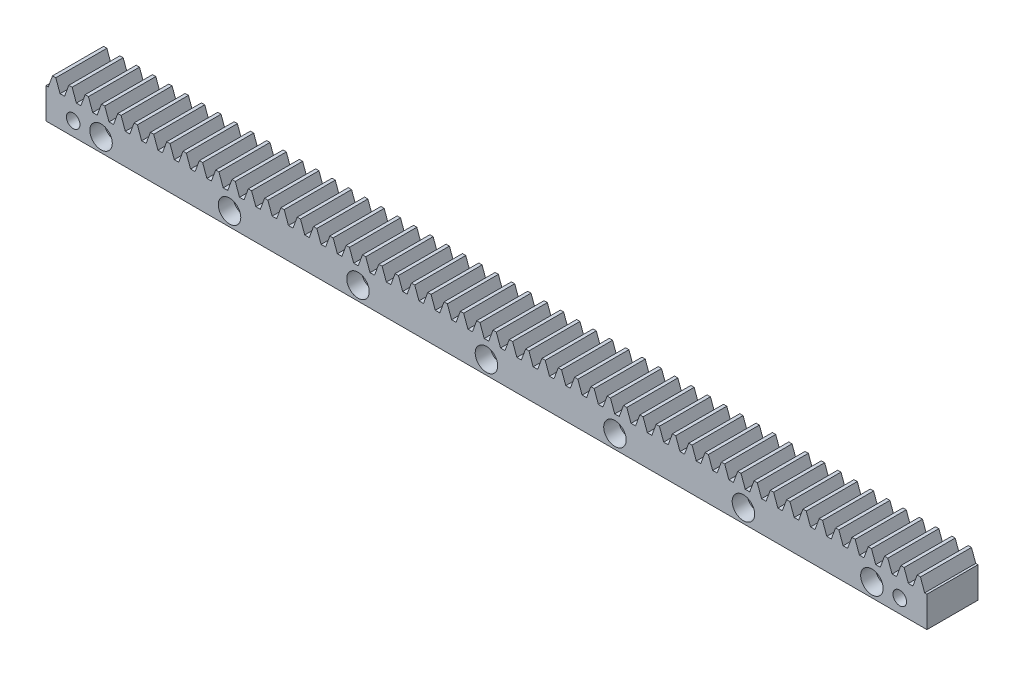
SolidWorks part; units mm, degrees
extrude "Blank" add sketch "BlankSke" against normal blind 59
sketch "BlankSke" plane through (0, 0, 0) normal (0, 0, 1) x (1, 0, 0)
  line L1 (0, 0) -> (1017.88, 0)
  line L2 (0, 0) -> (0, 49)
  line L3 (0, 49) -> (1017.88, 49)
  line L4 (1017.88, 0) -> (1017.88, 49)
  dimension "Length" = 1017.88
ref_plane "Plane1" through (0, 0, 0) normal (0, 0, 1) x (1, 0, 0)
ref_plane "Plane2" through (0, 0, 0) normal (0, 1, 0) x (1, 0, 0)
ref_plane "Plane3" through (0, 0, 0) normal (1, 0, 0) x (0, 0, -1)
sketch "HoldingSke" plane through (0, 0, 0) normal (0, 1, 0) x (1, 0, 0)
  line L0 (0, 0) -> (0.0232, 0.165)
  line L1 (-15, 0) -> (100, 0) construction
  line L2 (0, 0) -> (-2.1039, 2.3779)
  line L3 (0, 0) -> (-11.863, 4.5341)
  line L4 (0, 0) -> (4.8292, 7.1596)
  line L5 (0, 0) -> (-23.7986, -8.8762)
  line L6 (0, 0) -> (-10.5278, -7.1032)
  line L9 (-71.009, 38.7566) -> (885.4854, 386.8921)
  line L10 (-76.2, 8.3779) -> (-33.2, 8.3779)
  line L11 (0, 0) -> (-59, 0)
  line L12 (-76.2, 101.6) -> (-75.993, 101.6)
  line L13 (24.9733, 27.94) -> (52.9518, 28.4284)
  line L14 (24.9733, 27.94) -> (24.9743, 27.94)
  line L15 (24.9733, 27.94) -> (100.4006, 29.5858)
  circle A0 centre (0, 0) radius 19.05
  circle A1 centre (0, 0) radius 21.5
  circle A2 centre (0, 0) radius 12.7
  dimension "Num_teeth" = 56
  dimension "Width" = 59
  dimension "Length" = 1017.88
  dimension "Pitch_height" = 43
sketch "TooCutSkeIll" plane through (0, 0, 0) normal (0, 0, 1) x (1, 0, 0)
  line L0 (-7.4597, 48.8421) -> (-2.9631, 36.4876)
  line L1 (-1.5526, 35.5) -> (1.5526, 35.5)
  line L2 (2.9631, 36.4876) -> (7.4597, 48.8421)
  line L3 (1017.88, 49) -> (0, 49) construction
  line L4 (0, 0) -> (0, 64.897) construction
  line L5 (-13.208, 43) -> (12.954, 43) construction
  line L6 (0, 0) -> (1017.88, 0) construction
  line L7 (5.3334, 43) -> (5.3334, 48.7463) construction
  line L8 (-5.3334, 43) -> (-5.3334, 48.7463) construction
  line L9 (7.6853, 49) -> (7.6853, 49.0254)
  line L10 (-7.6853, 49) -> (-7.6853, 49.0254)
  line L11 (-7.6853, 49.0254) -> (7.6853, 49.0254)
  arc A0 (1.5526, 35.5) -> (2.9631, 36.4876) centre (1.5526, 37.001) ccw
  arc A1 (-2.9631, 36.4876) -> (-1.5526, 35.5) centre (-1.5526, 37.001) ccw
  arc A2 (7.6853, 49) -> (7.4597, 48.8421) centre (7.6853, 48.76) ccw
  arc A3 (-7.4597, 48.8421) -> (-7.6853, 49) centre (-7.6853, 48.76) ccw
  dimension "Addendum_plus" = 6.0254
  dimension "Pitch_height" = 43
  dimension "Pressure_angle" = 20
  dimension "Gap_width" = 10.6668
  dimension "Dedendum" = 7.5
extrude "ToothCutIll" [suppressed] cut sketch "TooCutSkeIll" against normal through all
sketch "TooCutSkeSim" plane through (0, 0, 0) normal (0, 0, 1) x (1, 0, 0)
  line L0 (2.6036, 35.5) -> (-2.6036, 35.5)
  line L1 (7.5265, 49.0254) -> (2.6036, 35.5)
  line L2 (0, 17.4625) -> (0, 53.467) construction
  line L3 (7.5265, 49.0254) -> (-7.5265, 49.0254)
  line L6 (-7.5265, 49.0254) -> (-2.6036, 35.5)
  line L9 (-5.3334, 43) -> (5.3334, 43) construction
  line L10 (0, 0) -> (1017.88, 0) construction
  line L11 (5.3334, 43) -> (5.3334, 53.467) construction
  line L12 (-5.3334, 43) -> (-5.3334, 53.467) construction
  dimension "Addendum_plus" = 6.0254
  dimension "Pitch_height" = 43
  dimension "Pressure_angle" = 20
  dimension "Gap_width" = 10.6668
  dimension "Dedendum" = 7.5
extrude "ToothCutSim" cut sketch "TooCutSkeSim" against normal through all
pattern_linear "TeethCuts" count 56 spacing 18.8496 along (1, 0, 0) of "ToothCutIll", "ToothCutSim"
sketch "Sketch2" plane through (0, 0, 0) normal (0, 0, 1) x (1, 0, 0)
  line L0 (0, 35.5) -> (0, 0) construction
  line L1 (0, 0) -> (1017.88, 0) construction
  line L2 (1017.88, 0) -> (1017.88, 35.5) construction
  circle A0 centre (31.4, 16) radius 7.85
  circle A1 centre (986.48, 16) radius 7.85
  dimension "D1" = 15.7
  dimension "D5" = 15.7
  dimension "D2" = 31.4
  dimension "D3" = 16
  dimension "D4" = 16
  dimension "D6" = 31.4
extrude "Cut-Extrude1" cut sketch "Sketch2" against normal blind 202
sketch "Sketch3" plane through (0, 0, 0) normal (0, 0, 1) x (1, 0, 0)
  line L0 (0, 35.5) -> (0, 0) construction
  circle A0 centre (63.6, 16) radius 9
  dimension "D1" = 18
  dimension "D2" = 63.6
extrude "Cut-Extrude2" cut sketch "Sketch3" against normal blind 202
sketch "Sketch4" plane through (0, 0, 0) normal (0, 0, 1) x (1, 0, 0)
  circle A0 centre (63.6, 16) radius 13
  dimension "D1" = 26
extrude "Cut-Extrude3" cut sketch "Sketch4" against normal blind 17
sketch "Sketch5" plane through (0, 0, 0) normal (0, 0, 1) x (1, 0, 0)
  line L0 (63.6, 16) -> (31.4, 16)
  line L1 (986.48, 16) -> (954.28, 16)
  dimension "D1" = 32.2
  dimension "D2" = 32.2
pattern_linear "LPattern1" count 2 spacing 890.68 along (1, 0, 0) of "Cut-Extrude2", "Cut-Extrude3"
pattern_linear "LPattern2" count 6 spacing 148.4467 along (1, 0, 0) of "Cut-Extrude2", "Cut-Extrude3"
equation "' \"Module@HoldingSke\" = 6.35"
equation "' \"Num_teeth@HoldingSke\" = 12"
equation "' \"Ap@HoldingSke\" =  20"
equation "' \"Ap@HoldingSke\" = 20"
equation "' \"Width@HoldingSke\" = 0.25 * 25.4"
equation "' \"Show_teeth@HoldingSke\" = 500"
equation "' \"Backlash@HoldingSke\" = 0.009 * 25.4"
equation "' \"Addendum_fac@HoldingSke\" = 1.0"
equation "' \"Dedendum_fac@HoldingSke\" = 1.25"
equation "' \"Dedendum_add@HoldingSke\" = 0.00005 * 25.4"
equation "' \"Clearance_fac@HoldingSke\" = 0.25"
equation "' \"Pitch_height@HoldingSke\" = 1 * 25.4"
equation "' \"Length@HoldingSke\" = 4.71 * 25.4"
equation "\"Pitch@HoldingSke\" = 1 / \"Module@HoldingSke\""
equation "\"MPH@HoldingSke\" = \"Dedendum_fac@HoldingSke\" / \"Pitch@HoldingSke\" + 2 * \"Dedendum_add@HoldingSke\" + 0.002 * 25.4"
equation "\"MPH@HoldingSke\" = ((sgn( \"MPH@HoldingSke\" - \"Pitch_height@HoldingSke\")+1)*( \"MPH@HoldingSke\" - \"Pitch_height@HoldingSke\"))/2 + \"Pitch_height@HoldingSke\""
equation "\"Blank_height@BlankSke\" = \"Pitch_height@HoldingSke\" + \"Addendum_fac@HoldingSke\"  / \"Pitch@HoldingSke\" "
equation "\"Length@BlankSke\" =  \"Length@HoldingSke\""
equation "\"Face_width@Blank\" = \"Width@HoldingSke\""
equation "\"Pressure_angle@TooCutSkeIll\" = \"Ap@HoldingSke\""
equation "\"Addendum_plus@TooCutSkeIll\" =  \"Addendum_fac@HoldingSke\"  / \"Pitch@HoldingSke\" + 0.001 *25.4"
equation "\"Dedendum@TooCutSkeIll\" = \"Dedendum_fac@HoldingSke\"  / \"Pitch@HoldingSke\""
equation "\"Pitch_height@TooCutSkeIll\" =  \"MPH@HoldingSke\""
equation "\"Gap_width@TooCutSkeIll\" = 3.14159265 / 2 / \"Pitch@HoldingSke\" + 6 * \"Backlash@HoldingSke\""
equation "\"Pressure_angle@TooCutSkeSim\" = \"Ap@HoldingSke\""
equation "\"Addendum_plus@TooCutSkeSim\" =  \"Addendum_fac@HoldingSke\"  / \"Pitch@HoldingSke\" + 0.001 * 25.4"
equation "\"Dedendum@TooCutSkeSim\" = \"Dedendum_fac@HoldingSke\"  / \"Pitch@HoldingSke\""
equation "\"Pitch_height@TooCutSkeSim\" =  \"MPH@HoldingSke\""
equation "\"Gap_width@TooCutSkeSim\" = 3.14159265 / 2 / \"Pitch@HoldingSke\" + 6 * \"Backlash@HoldingSke\""
equation "\"Root_fillet@TooCutSkeIll\" = \"Clearance_fac@HoldingSke\" / \"Pitch@HoldingSke\" + \"Dedendum_add@HoldingSke\""
equation "\"Break_rad@TooCutSkeIll\" = 0.02 / \"Pitch@HoldingSke\" * 2"
equation "\"Linear_pitch@TeethCuts\" = 3.14159265 / \"Pitch@HoldingSke\""
equation "\"Num_teeth@HoldingSke\" = int( ( \"Length@HoldingSke\" + 0 ) / (3.14159265 / \"Pitch@HoldingSke\")) + 0.9999  + 1"
equation " \"Num_teeth@TeethCuts\" = int( \"Show_teeth@HoldingSke\" ) + 1"
equation " \"Num_teeth@TeethCuts\" = ((sgn( \"Num_teeth@TeethCuts\" - \"Num_teeth@HoldingSke\" )-1)*( \"Num_teeth@TeethCuts\" - \"Num_teeth@HoldingSke\" ))/-2+ \"Num_teeth@HoldingSke\""
equation " \"Num_teeth@TeethCuts\" = ((sgn( \"Num_teeth@TeethCuts\" - 2.0)+1)*( \"Num_teeth@TeethCuts\" - 2.0))/2 +2.0"
